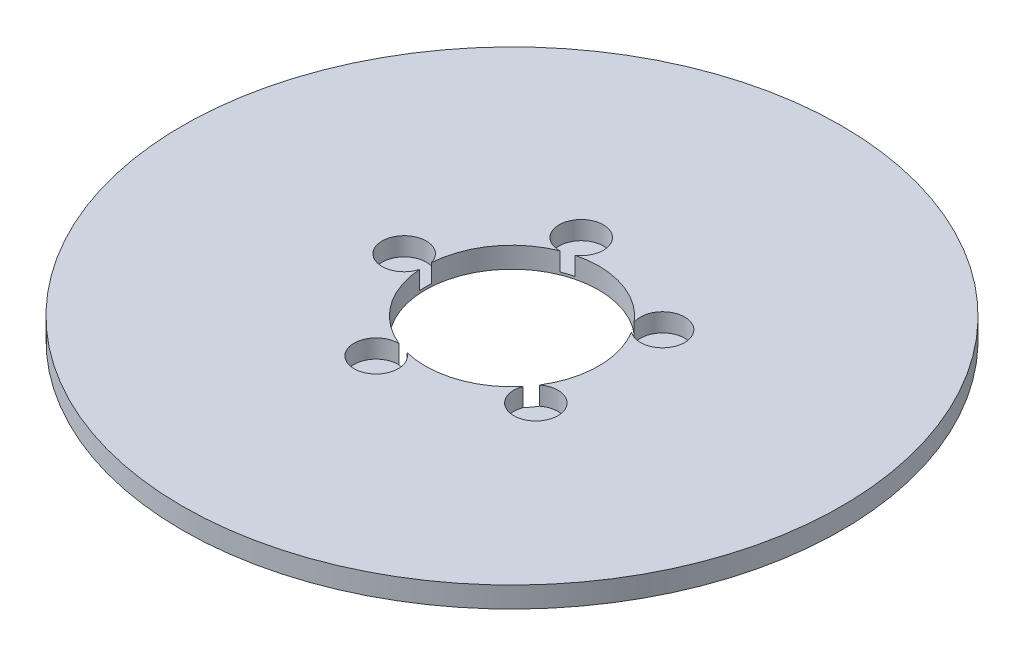
SolidWorks part; units mm, degrees
ref_plane "Front Plane" through (0, 0, 0) normal (0, 0, 1) x (1, 0, 0)
ref_plane "Top Plane" through (0, 0, 0) normal (0, 1, 0) x (1, 0, 0)
ref_plane "Right Plane" through (0, 0, 0) normal (1, 0, 0) x (0, 0, -1)
sketch "Sketch1" plane through (0, 0, 0) normal (0, 1, 0) x (1, 0, 0)
  circle A0 centre (0, 0) radius 95
  dimension "FLANGE_OD" = 190
extrude "Boss-Extrude1" add sketch "Sketch1" along normal blind 6
sketch "Sketch2" plane through (0, 0, 0) normal (0, 1, 0) x (1, 0, 0)
  circle A0 centre (0, 0) radius 25
  dimension "BORE_D" = 50
extrude "Cut-Extrude1" cut sketch "Sketch2" along normal through all
sketch "Sketch3" plane through (0, 6, 0) normal (0, 1, 0) x (1, 0, 0)
  circle A0 centre (0, 0) radius 31.0808 construction
  circle A1 centre (-31.0808, 0) radius 6.3775
  dimension "BOLT_D" = 12.755
  dimension "BOLT_PCD" = 62.1615
extrude "Cut-Extrude2" cut sketch "Sketch3" against normal blind 5.2962
pattern_circular "CirPattern1" count 5 over 360 about axis through (0, 0, 0) along (0, 1, 0) of "Cut-Extrude2"
